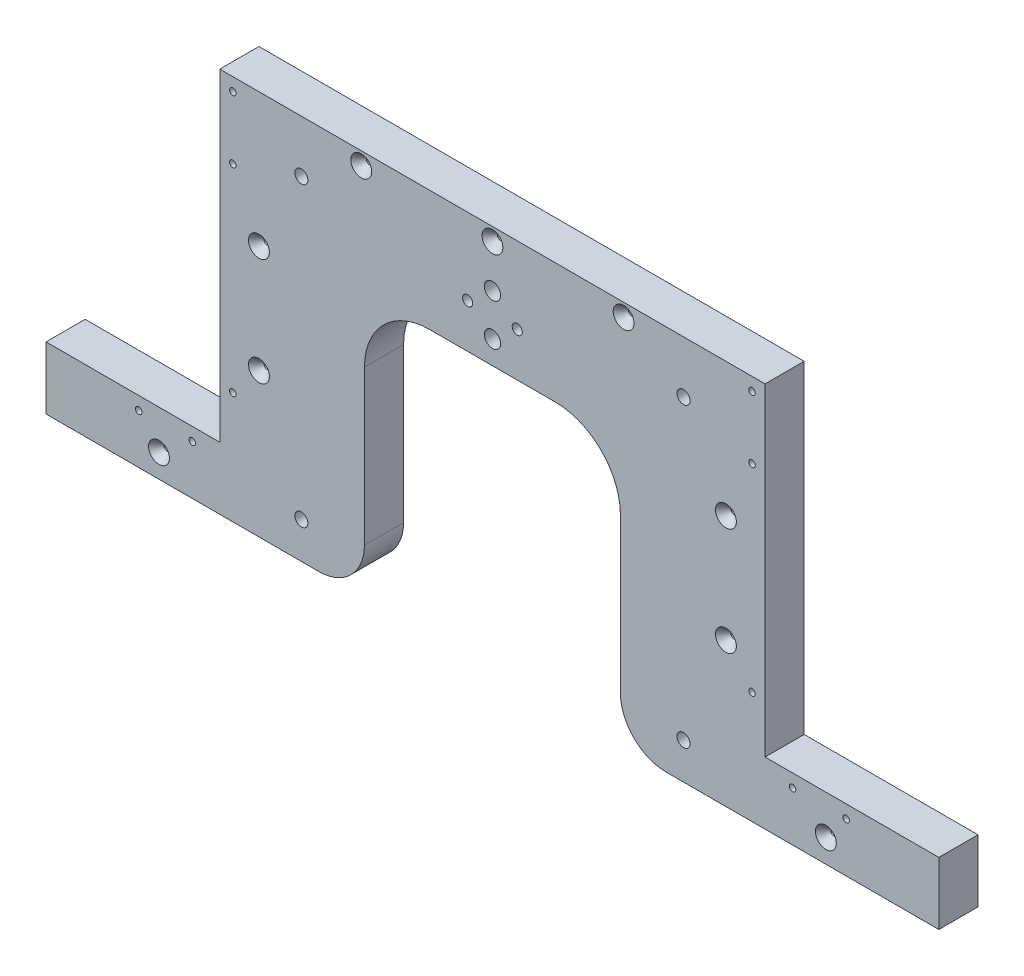
SolidWorks part; units mm, degrees
material "Beech"
ref_plane "Front Plane" through (0, 0, 0) normal (0, 0, 1) x (1, 0, 0)
ref_plane "Top Plane" through (0, 0, 0) normal (0, 1, 0) x (1, 0, 0)
ref_plane "Right Plane" through (0, 0, 0) normal (1, 0, 0) x (0, 0, -1)
sketch "Sketch1" plane through (0, 0, 0) normal (0, 0, 1) x (1, 0, 0)
  line L0 (-341.3045, -157.3) -> (-341.3045, -175)
  line L1 (-124.0045, 12.7) -> (-124.0045, -46)
  line L2 (-341.3045, -157.3) -> (-341.3045, -144.6)
  line L3 (-341.3045, -144.6) -> (-244.0045, -144.6)
  line L6 (-244.0045, -144.6) -> (-244.0045, 12.7)
  line L7 (-244.0045, 12.7) -> (-124.0045, 12.7)
  line L8 (-4.0045, 12.7) -> (-244.0045, 12.7) construction
  line L13 (-124.0045, -46) -> (-186.3045, -46)
  line L14 (-186.3045, -46) -> (-186.3045, -175)
  line L15 (-186.3045, -175) -> (-341.3045, -175)
  dimension "D2" = 17.7
  dimension "D1" = 12.7
  dimension "D6" = 58.7
  dimension "D7" = 155
extrude "Boss-Extrude2" add sketch "Sketch1" along normal blind 19.05 contours L13 L14 L15 L0 L2 L3 L6 L7 L1
fillet "Fillet1" radius 22.225 1 edges at (-186.3045, -175, 9.525)
fillet "Fillet2" radius 31.75 1 edges at (-186.3045, -46, 9.525)
sketch "Sketch6" plane through (-244.0045, 0, 0) normal (-1, 0, 0) x (0, 0, 1)
  line L4 (0, 12.7) -> (0, -144.6)
  line L5 (0, -144.6) -> (19.05, -144.6)
  line L6 (19.05, -144.6) -> (19.05, 12.7)
  line L7 (19.05, 12.7) -> (0, 12.7)
  line L8 (0, 12.7) -> (0, -144.6)
  line L9 (0, -144.6) -> (19.05, -144.6)
  line L10 (19.05, -144.6) -> (19.05, 12.7)
  line L11 (19.05, 12.7) -> (0, 12.7)
  dimension "D1" = 0
extrude "Boss-Extrude3" add sketch "Sketch6" along normal up to surface (12.7 mm away)
mirror "Mirror1" about plane through (-124.0045, 12.7, 19.05) normal (1, 0, 0) of "Fillet2", "Fillet1", "Boss-Extrude2", "Boss-Extrude3"
hole_wizard "5/16 (0.3125) Diameter Hole1" positions "Sketch2" profile "Sketch3" hole size "5/16" standard "ANSI Inch" end condition through all
sketch "Sketch2" plane through (0, 0, 0) normal (0, 0, -1) x (-1, 0, 0)
  circle A0 centre (124.0045, -14.4275) radius 3.5712 construction
  circle A1 centre (124.0045, -34.7475) radius 3.5712 construction
  point P0 (124.0045, -34.7475)
  point P2 (124.0045, -14.4275)
sketch "Sketch3" plane through (-124.0045, -34.7475, 0) normal (1, 0, 0) x (0, 1, 0)
  line L0 (0, 0) -> (0, 19.05)
  line L1 (0, 19.05) -> (3.9687, 19.05)
  line L2 (3.9687, 19.05) -> (3.9688, 0)
  line L5 (3.9688, 0) -> (0, 0)
  line L11 (0, -6.35) -> (0, 107.95) construction
  dimension "Thru Hole Dia." = 7.9375
  dimension "Thru Hole Depth" = 19.05
hole_wizard "#8 Clearance Hole1" positions "Sketch4" profile "Sketch5" hole size "#8" standard "ANSI Inch" end condition through all
sketch "Sketch4" plane through (0, 0, 19.05) normal (0, 0, 1) x (1, 0, 0)
  point P0 (-111.9272, -24.5875)
  point P2 (-136.0817, -24.5875)
sketch "Sketch5" plane through (-111.9272, -24.5875, 19.05) normal (1, 0, 0) x (0, -1, 0)
  line L0 (0, 0) -> (0, 19.05)
  line L1 (0, 19.05) -> (2.4574, 19.05)
  line L2 (2.4574, 19.05) -> (2.4574, 0)
  line L5 (2.4574, 0) -> (0, 0)
  line L11 (0, -6.35) -> (0, 107.95) construction
  dimension "Thru Hole Dia." = 4.9149
  dimension "Thru Hole Depth" = 19.05
hole_wizard "Hole1" positions "Sketch7" profile "Sketch8" legacy
sketch "Sketch7" plane through (-124.0045, -155.0243, 19.05) normal (0, 0, 1) x (1, 0, 0)
  point P15 (-162.3, -8.6257)
  point P34 (-113.65, 50.1576)
  point P36 (-113.65, 102.591)
  point P54 (162.3, -8.6257)
  point P55 (113.65, 50.1576)
  point P56 (113.65, 102.591)
  point P71 (63.85, 161.3743)
  point P73 (0, 161.3743)
  point P74 (-63.85, 161.3743)
sketch "Sketch8" plane through (-286.3045, -163.65, 19.05) normal (1, 0, 0) x (0, -1, 0)
  line L0 (0, 0) -> (0, 32.7039)
  line L1 (0, 32.7039) -> (1.5875, 31.75)
  line L2 (1.5875, 31.75) -> (1.5875, 4.0177)
  line L3 (1.5875, 4.0177) -> (5.08, 0)
  line L4 (5.08, 0) -> (0, 0)
  line L5 (0, -14.3089) -> (0, 102.4216) construction
  line L6 (0, 32.7039) -> (-1.5875, 31.75) construction
  line L7 (-1.5875, 4.0177) -> (-5.08, 0) construction
  dimension "Diameter" = 3.175
  dimension "Depth" = 31.75
  dimension "C-Sink Diameter" = 10.16
  dimension "C-Sink Angle" = 82
  dimension "Drill Angle" = 118
hole_wizard "Hole2" positions "Sketch9" profile "Sketch10" legacy
sketch "Sketch9" plane through (-124.0045, -155.0243, 0) normal (0, 0, -1) x (-1, 0, 0)
  line L21 (0, 109.0243) -> (0, 155.0243) construction
  point P37 (126.35, 161.3743)
  point P42 (146.0833, 4.0743)
  point P44 (172.1667, 4.0743)
  point P63 (126.35, 34.5243)
  point P65 (126.35, 130.9243)
  point P76 (-172.1667, 4.0743)
  point P77 (-146.0833, 4.0743)
  point P78 (-126.35, 34.5243)
  point P79 (-126.35, 130.9243)
  point P80 (-126.35, 161.3743)
sketch "Sketch10" plane through (-250.3545, 6.35, 0) normal (1, 0, 0) x (0, 1, 0)
  line L0 (0, 0) -> (0, 32.7039)
  line L1 (0, 32.7039) -> (1.5875, 31.75)
  line L2 (1.5875, 31.75) -> (1.5875, 4.0177)
  line L3 (1.5875, 4.0177) -> (5.08, 0)
  line L4 (5.08, 0) -> (0, 0)
  line L5 (0, -14.3089) -> (0, 102.4216) construction
  line L6 (0, 32.7039) -> (-1.5875, 31.75) construction
  line L7 (-1.5875, 4.0177) -> (-5.08, 0) construction
  dimension "Diameter" = 3.175
  dimension "Depth" = 31.75
  dimension "C-Sink Diameter" = 10.16
  dimension "C-Sink Angle" = 82
  dimension "Drill Angle" = 118
hole_wizard "1/4 (0.25) Diameter Hole1" positions "Sketch11" profile "Sketch12" hole size "1/4" standard "ANSI Inch" end condition through all
sketch "Sketch11" plane through (0, 0, 19.05) normal (0, 0, 1) x (1, 0, 0)
  point P0 (-217.017, -157.3)
  point P2 (-217.017, -12.7)
  point P4 (-30.992, -12.7)
  point P6 (-30.992, -157.3)
sketch "Sketch12" plane through (-217.017, -157.3, 19.05) normal (1, 0, 0) x (0, -1, 0)
  line L0 (0, 0) -> (0, 19.05)
  line L1 (0, 19.05) -> (3.175, 19.05)
  line L2 (3.175, 19.05) -> (3.175, 0)
  line L5 (3.175, 0) -> (0, 0)
  line L11 (0, -6.35) -> (0, 107.95) construction
  dimension "Thru Hole Dia." = 6.35
  dimension "Thru Hole Depth" = 19.05
